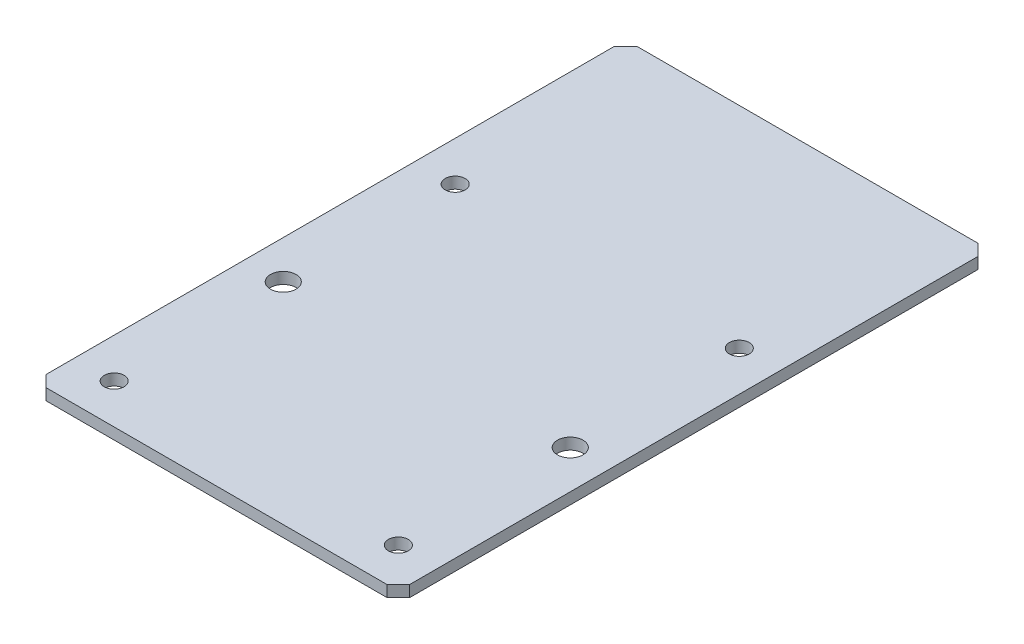
SolidWorks part; units mm, degrees
material "1060 Alloy"
ref_plane "Front Plane" through (0, 0, 0) normal (0, 0, 1) x (1, 0, 0)
ref_plane "Top Plane" through (0, 0, 0) normal (0, 1, 0) x (1, 0, 0)
ref_plane "Right Plane" through (0, 0, 0) normal (1, 0, 0) x (0, 0, -1)
sketch "Sketch1" plane through (0, 0, 0) normal (0, 0, 1) x (1, 0, 0)
  line L0 (-32, 0) -> (32, 0)
  line L1 (0, 0) -> (0, 13.1388) construction
  dimension "D1" = 64
sheet metal parameters "Sheet-Metal1" thickness 2 parameters "D1"=2
base flange "Base-Flange1" sketch "Sketch1" end condition blind depth 74 reverse direction no thickness 2 reverse thickness direction no bend radius 2
sketch "Sketch2" plane through (0, 0, 0) normal (0, 1, 0) x (1, 0, 0)
  line L0 (0, -7) -> (0, 0) construction
  line L1 (-25, -7) -> (25, -7) construction
  line L2 (-25, -7) -> (-25, -67) construction
  line L3 (-25, -67) -> (25, -67) construction
  line L4 (25, -7) -> (25, -67) construction
  line L5 (-25, -37) -> (-32, -37) construction
  line L6 (-32, -74) -> (32, -74) construction
  line L7 (-32, -74) -> (-32, 0) construction
  line L8 (32, -74) -> (32, 0) construction
  circle A0 centre (-25, -7) radius 1.75
  circle A1 centre (-25, -67) radius 1.75
  circle A2 centre (25, -67) radius 1.75
  circle A3 centre (25, -7) radius 1.75
  dimension "D1" = 3.5
  dimension "D3" = 7
  dimension "D2" = 7
extrude "Cut-Extrude1" cut sketch "Sketch2" against normal blind 10 normal cut yes
chamfer "Chamfer1" distance 2 angle 45 2 edges at (32, -1, 74) (-32, -1, 74)
sketch "Sketch8" plane through (0, 0, 0) normal (0, 1, 0) x (1, 0, 0)
  line L1 (-32, 0) -> (32, 0)
  line L2 (-32, 0) -> (-32, 30)
  line L3 (-32, 30) -> (32, 30)
  line L4 (32, 0) -> (32, 30)
  dimension "D1" = 30
base flange "Tab1" sketch "Sketch8" thickness 2 reverse thickness direction no parameters "D1"=2
chamfer "Chamfer2" distance 2 angle 45 2 edges at (32, -1, -30) (-32, -1, -30)
sketch "Sketch9" plane through (0, 0, 0) normal (0, 1, 0) x (1, 0, 0)
  line L0 (-25, -7) -> (25, -67) construction
  line L1 (0, -37) -> (-25.25, -37) construction
  line L2 (0, -37) -> (25.25, -37) construction
  circle A0 centre (-25.25, -37) radius 2.25
  circle A1 centre (25.25, -37) radius 2.25
  dimension "D1" = 4.5
  dimension "D2" = 50.5
extrude "Cut-Extrude2" cut sketch "Sketch9" against normal up to next normal cut yes
flat pattern "Flat-Pattern1" [suppressed]
sketch "Bend-Lines1" plane through (0, 0, 0) normal (0, 1, 0) x (-1, 0, 0)
